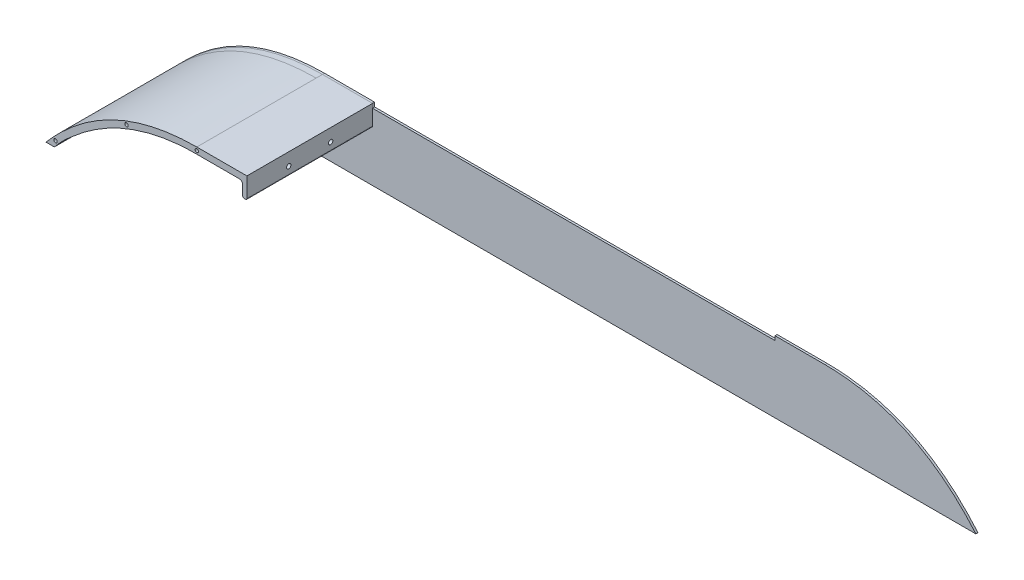
SolidWorks part; units mm, degrees
ref_plane "Front Plane" through (0, 0, 0) normal (0, 0, 1) x (1, 0, 0)
ref_plane "Top Plane" through (0, 0, 0) normal (0, 1, 0) x (1, 0, 0)
ref_plane "Right Plane" through (0, 0, 0) normal (1, 0, 0) x (0, 0, -1)
sketch "Sketch1" plane through (0, 0, 0) normal (0, 0, 1) x (1, 0, 0)
  line L0 (0, 0) -> (-304.8, 0)
  line L1 (0, 0) -> (609.6, 0)
  line L2 (0, 0) -> (0, 107.95) construction
  line L3 (0, 107.95) -> (609.6, 107.95)
  line L4 (609.6, 0) -> (609.6, 107.95) construction
  line L5 (609.6, 0) -> (914.4, 0)
  line L6 (304.8, -1000) -> (304.8, 49000) construction
  line L7 (0, 107.95) -> (-76.2, 107.95)
  line L8 (609.6, 107.95) -> (685.8, 107.95)
  spline S0 degree 2 poles (-304.8, 0) (-213.404, 107.36) (-76.2, 107.95) knots 0 0 0 1 1 1
  spline S1 degree 2 poles (914.4, 0) (823.004, 107.36) (685.8, 107.95) knots 0 0 0 1 1 1
  point P11 (304.8, 0)
  dimension "D1" = 609.6
  dimension "D2" = 107.95
  dimension "D3" = 304.8
  dimension "D4" = 76.2
extrude "Boss-Extrude1" add sketch "Sketch1" along normal blind 3.175
sketch "Sketch2" plane through (0, 0, 3.175) normal (0, 0, 1) x (1, 0, 0)
  line L8 (685.8, 107.95) -> (-76.2, 107.95) construction
  line L11 (0, 107.95) -> (609.6, 107.95)
  line L12 (0, 107.95) -> (0, 101.6) construction
  line L13 (0, 101.6) -> (609.6, 101.6)
  line L14 (609.6, 107.95) -> (609.6, 101.6) construction
  line L15 (-0.254, 107.95) -> (-0.254, 101.6)
  line L16 (609.854, 107.95) -> (609.854, 101.6)
  line L19 (609.6, 107.95) -> (609.854, 107.95)
  line L20 (609.6, 101.6) -> (609.854, 101.6)
  line L21 (-0.254, 107.95) -> (0, 107.95)
  line L22 (-0.254, 101.6) -> (0, 101.6)
  dimension "D1" = 609.6
  dimension "D2" = 6.35
  dimension "D3" = 0.254
  dimension "D4" = 0.254
extrude "Cut-Extrude1" cut sketch "Sketch2" against normal through all
sketch "Sketch3" plane through (0, 0, 3.175) normal (0, 0, 1) x (1, 0, 0)
  line L5 (-76.0908, 82.5502) -> (-76.2, 107.95) construction
  line L6 (685.8, 107.95) -> (609.854, 107.95)
  line L7 (609.854, 107.95) -> (609.854, 101.6)
  line L8 (609.854, 101.6) -> (-0.254, 101.6)
  line L9 (-0.254, 101.6) -> (-0.254, 107.95)
  line L10 (-0.254, 107.95) -> (-76.2, 107.95)
  line L11 (-304.8, 0) -> (914.4, 0)
  line L19 (-304.8, 0) -> (-254.508, 0)
  line L20 (-304.8, 0) -> (914.4, 0) construction
  line L21 (-254.508, 0) -> (-254.508, 15.3448)
  line L22 (-76.2, 107.95) -> (-0.254, 107.95)
  line L23 (-0.254, 107.95) -> (-0.254, 76.2)
  line L24 (-0.254, 76.2) -> (-6.604, 76.2)
  line L25 (-6.604, 76.2) -> (-6.604, 82.5502)
  line L26 (-6.604, 82.5502) -> (-76.0908, 82.5502)
  parabola Q2 (-76.2, 107.95) -> (-304.8, 0) focus (-138.8032, -41.5009) apex (-192.9562, 84.7198)
  parabola Q3 (914.4, 0) -> (685.8, 107.95) focus (748.4032, -41.5009) apex (802.5562, 84.7198)
  parabola Q4 (-76.2, 107.95) -> (-304.8, 0) focus (-138.8032, -41.5009) apex (-192.9562, 84.7198)
  spline S0 degree 1 poles (-76.0908, 82.5502) (-285.4592, -16.4649) knots 0 0 1 1 construction
  spline S1 degree 3 poles (-76.0908, 82.5502) (-78.7263, 82.5389) (-84.0207, 82.4515) (-94.414, 82.0204) (-107.175, 81.0024) (-122.0857, 79.0209) (-140.2937, 75.5918) (-157.8592, 70.8643) (-175.9104, 64.4537) (-194.5198, 56.4637) (-212.4049, 46.7322) (-228.6865, 35.996) (-240.414, 27.3) (-249.9299, 19.4397) (-257.5609, 12.6326) (-263.3873, 7.1473) (-268.2089, 2.3627) (-271.8925, -1.4301) (-275.5622, -5.3024) (-280.0978, -10.2646) (-283.6939, -14.3913) (-285.4592, -16.4649) knots 0.497516 0.497516 0.497516 0.497516 0.497684 0.497853 0.498189 0.498526 0.498863 0.499456 0.499793 0.50021 0.500884 0.501221 0.501558 0.501878 0.502046 0.502231 0.502399 0.502483 0.502568 0.502737 0.502905 0.502905 0.502905 0.502905 only from (-76.0908, 82.5502) to (-270.5007, 0) construction
  spline S2 degree 2 poles (-254.508, 15.3448) (-177.7983, 82.8932) (-76.0908, 82.5502) knots 0 0 0 1 1 1
  dimension "D2" = 31.75
  dimension "D3" = 6.35
  dimension "D5" = 50.292
  dimension "D1" = 0
  dimension "D4" = 25.4
extrude "Boss-Extrude2" add sketch "Sketch3" along normal blind 9.525
sketch "Sketch5" plane through (0, 0, 12.7) normal (0, 0, 1) x (1, 0, 0)
  line L7 (-304.8, 0) -> (-292.1, 0)
  line L8 (-76.0372, 98.4251) -> (-6.604, 98.4251)
  line L9 (-6.604, 98.4251) -> (-6.604, 82.5502)
  line L14 (-304.8, 0) -> (-254.508, 0)
  line L15 (-254.508, 0) -> (-254.508, 15.3448)
  line L16 (-76.0908, 82.5502) -> (-6.604, 82.5502)
  line L17 (-6.604, 82.5502) -> (-6.604, 76.2)
  line L18 (-6.604, 76.2) -> (-0.254, 76.2)
  line L19 (-0.254, 76.2) -> (-0.254, 107.95)
  line L20 (-0.254, 107.95) -> (-76.2, 107.95)
  line L24 (-6.604, 82.5502) -> (-6.604, 76.2)
  line L25 (-6.604, 76.2) -> (-0.254, 76.2)
  line L26 (-0.254, 76.2) -> (-0.254, 107.95)
  line L27 (-0.254, 107.95) -> (-76.2, 107.95)
  parabola Q4 (-76.2, 107.95) -> (-304.8, 0) focus (-138.8032, -41.5009) apex (-192.9562, 84.7198)
  parabola Q5 (-254.508, 15.3448) -> (-76.0908, 82.5502) focus (-126.3995, -51.2914) apex (-169.7975, 66.5726)
  parabola Q6 (-76.2, 107.95) -> (-304.8, 0) focus (-138.8032, -41.5009) apex (-192.9562, 84.7198)
  parabola Q7 (-254.508, 15.3448) -> (-76.0908, 82.5502) focus (-126.3995, -51.2914) apex (-169.7975, 66.5726) construction
  spline S0 degree 1 poles (-264.9993, 27.259) (-76.0372, 98.4251) knots 0 0 1 1 construction
  spline S1 degree 3 poles (-264.9993, 27.259) (-263.3249, 28.7335) (-259.9376, 31.6547) (-253.107, 37.2998) (-244.419, 44.0244) (-233.7687, 51.5472) (-219.2659, 60.8476) (-200.5783, 71.0931) (-177.2837, 81.1523) (-153.1553, 88.9561) (-132.3866, 93.5719) (-115.3933, 96.1333) (-102.4647, 97.4901) (-91.5371, 98.1519) (-82.7134, 98.4012) (-78.2591, 98.4326) (-76.0372, 98.4251) knots 0.497832 0.497832 0.497832 0.497832 0.497965 0.498098 0.498363 0.498629 0.498895 0.499427 0.499958 0.50049 0.501022 0.501287 0.501553 0.501819 0.501952 0.502085 0.502085 0.502085 0.502085
  spline S2 degree 2 poles (-264.9993, 27.259) (-280.0432, 15.0907) (-292.1, 0) knots 0 0 0 1 1 1
  dimension "D3" = 12.7
  dimension "D1" = 0
  dimension "D2" = 15.875
extrude "Boss-Extrude3" add sketch "Sketch5" along normal blind 180.975
sketch "Sketch6" plane through (0, 0, 12.7) normal (0, 0, 1) x (1, 0, 0)
  line L1 (-254.508, 0) -> (-226.4253, 0)
  line L2 (-254.508, 0) -> (-254.508, 28.575)
  line L3 (-254.508, 28.575) -> (-226.4253, 28.575)
  line L4 (-226.4253, 0) -> (-226.4253, 28.575)
  dimension "D1" = 28.575
extrude "Cut-Extrude2" cut sketch "Sketch6" against normal up to surface (9.525 mm away) up to face at (204.1979, 60.3971, 3.175)
sketch "Sketch7" plane through (0, 0, 12.7) normal (0, 0, 1) x (1, 0, 0)
  line L0 (-292.1, 0) -> (-254.508, 0) construction
  line L1 (-254.508, 0) -> (-254.508, 28.575) construction
  line L2 (-76.0651, 90.1702) -> (-9.6958, 90.1702) construction
  line L3 (-6.604, 98.4251) -> (-6.604, 76.2) construction
  circle A0 centre (-267.208, 10.16) radius 3.275
  circle A1 centre (-175.3658, 72.6223) radius 3.275
  circle A3 centre (-57.404, 90.1702) radius 3.275
  parabola Q0 (-238.3942, 28.575) -> (-76.0908, 82.5502) focus (-126.3995, -51.2914) apex (-169.7975, 66.5726) construction
  parabola Q1 (-238.3942, 28.575) -> (-76.0908, 82.5502) focus (-126.3995, -51.2914) apex (-169.7975, 66.5726) construction
  spline S0 degree 1 poles (-243.0182, 34.6317) (-76.0651, 90.1702) knots 0 0 1 1 construction
  spline S1 degree 3 poles (-243.0182, 34.6317) (-239.9935, 36.9409) (-233.8311, 41.4586) (-224.4638, 47.7679) (-214.9157, 53.6525) (-202.0674, 60.8581) (-190.551, 66.4075) (-178.8009, 71.3309) (-171.8366, 73.9914) (-159.5844, 78.2202) (-143.5556, 82.8056) (-125.3458, 86.3973) (-110.4698, 88.391) (-99.1613, 89.4468) (-89.6088, 89.961) (-81.8979, 90.1535) (-78.0064, 90.1767) (-76.0651, 90.1702) knots 0.498271 0.498271 0.498271 0.498271 0.49851 0.498748 0.498986 0.499225 0.499694 0.499813 0.500051 0.500178 0.500655 0.501131 0.50137 0.501608 0.501846 0.501966 0.502085 0.502085 0.502085 0.502085 construction
  dimension "D1" = 6.55
  dimension "D5" = 6.55
  dimension "D6" = 6.55
  dimension "D2" = 10.16
  dimension "D4" = 12.7
  dimension "D7" = 50.8
  dimension "D3" = 7.62
extrude "Cut-Extrude3" cut sketch "Sketch7" against normal through all
sketch "Sketch8" plane through (-0.254, 0, 0) normal (1, 0, 0) x (0, 0, -1)
  line L0 (-1151.3542, 88.9) -> (48848.6458, 88.9) construction
  line L1 (-193.675, 76.2) -> (-3.175, 76.2) construction
  line L2 (-3.175, 76.2) -> (-3.175, 101.6) construction
  circle A2 centre (-66.675, 88.9) radius 3.325
  circle A5 centre (-130.175, 88.9) radius 3.325
  dimension "D2" = 6.65
  dimension "D4" = 63.5
  dimension "D1" = 12.7
  dimension "D3" = 2
extrude "Cut-Extrude5" cut sketch "Sketch8" against normal up to surface (6.35 mm away) up to face at (-6.604, 85.7251, 69.85)
sketch "Sketch9" plane through (0, 0, 193.675) normal (0, 0, 1) x (1, 0, 0)
  circle A0 centre (-290.3708, 9.1426) radius 2.6
  circle A1 centre (-182.7594, 83.8165) radius 2.6
  circle A2 centre (-76.1798, 103.25) radius 2.6
  parabola Q0 (-76.2, 107.95) -> (-304.8, 0) focus (-138.8032, -41.5009) apex (-192.9562, 84.7198) construction
  parabola Q1 (-76.2, 107.95) -> (-304.8, 0) focus (-138.8032, -41.5009) apex (-192.9562, 84.7198) construction
  spline S0 degree 1 poles (-76.1798, 103.25) (-301.2212, -3.0467) knots 0 0 1 1 construction
  spline S1 degree 3 poles (-76.1798, 103.25) (-78.9851, 103.238) (-84.6167, 103.1451) (-95.7036, 102.6853) (-109.3519, 101.5971) (-125.3575, 99.4709) (-145.1456, 95.7451) (-161.7727, 91.2541) (-177.9517, 85.7316) (-188.5878, 81.5829) (-206.0869, 73.7491) (-227.5653, 62.0602) (-249.2337, 46.8941) (-265.8815, 33.1047) (-277.7275, 22.2059) (-286.3, 13.5161) (-292.1052, 7.2837) (-296.2196, 2.7435) (-299.3516, -0.8505) (-301.2212, -3.0467) knots 0.497516 0.497516 0.497516 0.497516 0.497684 0.497853 0.498189 0.498526 0.498863 0.499468 0.499636 0.499973 0.50021 0.500884 0.501558 0.501895 0.502231 0.502544 0.502628 0.502737 0.502905 0.502905 0.502905 0.502905 construction
  dimension "D2" = 5.2
  dimension "D3" = 5.2
  dimension "D4" = 5.2
  dimension "D1" = 4.7
extrude "Cut-Extrude6" cut sketch "Sketch9" against normal blind 12.7
sketch "Sketch11" plane through (-254.508, 0, 0) normal (1, 0, 0) x (0, 0, -1)
  line L0 (-3.175, 0) -> (-3.175, 28.575) construction
  line L1 (-12.7, 0) -> (-3.175, 0) construction
  circle A0 centre (-7.1374, 3.9751) radius 1.9
  circle A3 centre (-7.1374, 21.4251) radius 1.9
  dimension "D3" = 3.8
  dimension "D1" = 3.9624
  dimension "D2" = 3.9751
  dimension "D4" = 2
extrude "Boss-Extrude5" add sketch "Sketch11" along normal blind 10.16
fillet "Fillet1" radius 5 1 edges at (-6.604, 98.4251, 103.1875)
fillet "Fillet2" radius 2 2 edges at (-238.3942, 28.575, 7.9375) (-254.508, 28.575, 7.9375)
fillet "Fillet3" radius 1 1 edges at (-292.1, 0, 103.1875)
fillet "Fillet4" radius 2 3 edges at (-6.604, 82.5502, 7.9375) (-0.254, 76.2, 98.425) (-6.604, 76.2, 98.425)
split "Split1" bodies to split 110 resulting bodies 125 126 split by face at (88.8021, 59.1412, 3.175)
